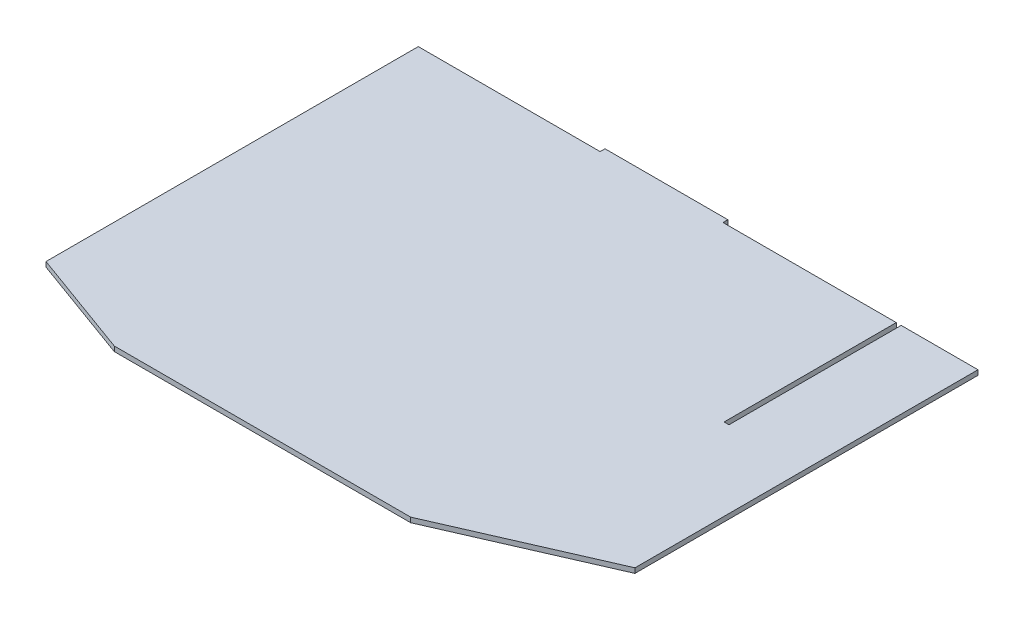
SolidWorks part; units mm, degrees
material "6061-T6 (SS)"
ref_plane "X-Y Datum" through (0, 0, 0) normal (0, 0, 1) x (1, 0, 0)
ref_plane "X-Z Datum" through (0, 0, 0) normal (0, 1, 0) x (1, 0, 0)
ref_plane "Y-Z Datum" through (0, 0, 0) normal (1, 0, 0) x (0, 0, -1)
sketch "Sketch1" plane through (0, 0, 0) normal (0, 0, 1) x (1, 0, 0)
  line L1 (-155.6385, -1.5875) -> (155.6385, -1.5875)
  line L2 (-155.6385, -1.5875) -> (-155.6385, 1.5875)
  line L3 (-155.6385, 1.5875) -> (155.6385, 1.5875)
  line L4 (155.6385, -1.5875) -> (155.6385, 1.5875)
  line L5 (-155.6385, -1.5875) -> (155.6385, 1.5875) construction
  line L6 (-155.6385, 1.5875) -> (155.6385, -1.5875) construction
  point P0 (0, 0)
  dimension "D1" = 3.175
  dimension "D2" = 311.277
extrude "Boss-Extrude1" add sketch "Sketch1" along normal blind 267.83
sketch "Sketch3" plane through (155.6385, 0, 0) normal (1, 0, 0) x (0, 0, -1)
  line L0 (-267.83, 1.5875) -> (0, 1.5875) construction
  line L1 (-267.83, -1.5875) -> (-112.128, -1.5875)
  line L2 (-267.83, -1.5875) -> (-267.83, 1.5875)
  line L3 (-267.83, 1.5875) -> (-112.128, 1.5875)
  line L4 (-112.128, -1.5875) -> (-112.128, 1.5875)
  dimension "D1" = 155.702
extrude "Boss-Extrude3" add sketch "Sketch3" along normal blind 3.175
sketch "Sketch4" plane through (0, 0, 267.83) normal (0, 0, 1) x (1, 0, 0)
  line L1 (158.8135, -1.5875) -> (208.8515, -1.5875)
  line L2 (158.8135, -1.5875) -> (158.8135, 1.5875)
  line L3 (158.8135, 1.5875) -> (208.8515, 1.5875)
  line L4 (208.8515, -1.5875) -> (208.8515, 1.5875)
  dimension "D1" = 3.175
  dimension "D2" = 50.038
extrude "Boss-Extrude4" add sketch "Sketch4" against normal blind 267.83
sketch "Sketch6" plane through (0, 1.5875, 0) normal (0, 1, 0) x (1, 0, 0)
  line L0 (107.2515, -267.83) -> (107.2515, -223.38)
  line L1 (208.8515, -267.83) -> (-155.6385, -267.83) construction
  line L2 (208.8515, -223.38) -> (107.2515, -223.38)
  line L3 (208.8515, 0) -> (208.8515, -267.83) construction
  line L4 (107.2515, -267.83) -> (208.8515, -223.38)
  line M9 (-155.6385, -267.83) -> (208.8515, -267.83)
  line M10 (208.8515, -267.83) -> (208.8515, 0)
  dimension "D1" = 44.45
  dimension "D2" = 101.6
extrude "Cut-Extrude1" cut sketch "Sketch6" against normal through all contours L4 M9 M10 region at (174.9848, 1.5875, 253.0133)
sketch "Sketch8" plane through (0, 0, 0) normal (0, 0, -1) x (-1, 0, 0)
  line L1 (37.216, 1.5875) -> (-42.784, 1.5875)
  line L2 (37.216, 1.5875) -> (37.216, -1.5875)
  line L3 (37.216, -1.5875) -> (-42.784, -1.5875)
  line L4 (-42.784, 1.5875) -> (-42.784, -1.5875)
extrude "Boss-Extrude6" add sketch "Sketch8" along normal blind 3.175
sketch "Sketch11" plane through (0, -1.5875, 0) normal (0, -1, 0) x (1, 0, 0)
  line L0 (-85.7885, 267.83) -> (-85.7885, 242.43)
  line L1 (-155.6385, 267.83) -> (107.2515, 267.83) construction
  line L2 (-155.6385, 242.43) -> (-85.7885, 242.43)
  line L3 (-155.6385, 267.83) -> (-155.6385, 137.414) construction
  line L4 (-155.6385, 242.43) -> (-85.7885, 267.83)
  line M4 (-155.6385, 267.83) -> (-155.6385, 137.414)
  line M18 (107.2515, 267.83) -> (-155.6385, 267.83)
  dimension "D1" = 69.85
  dimension "D2" = 25.4
extrude "Cut-Extrude3" cut sketch "Sketch11" against normal through all contours L4 M4 M18 region at (-132.3552, -1.5875, 259.3633)
